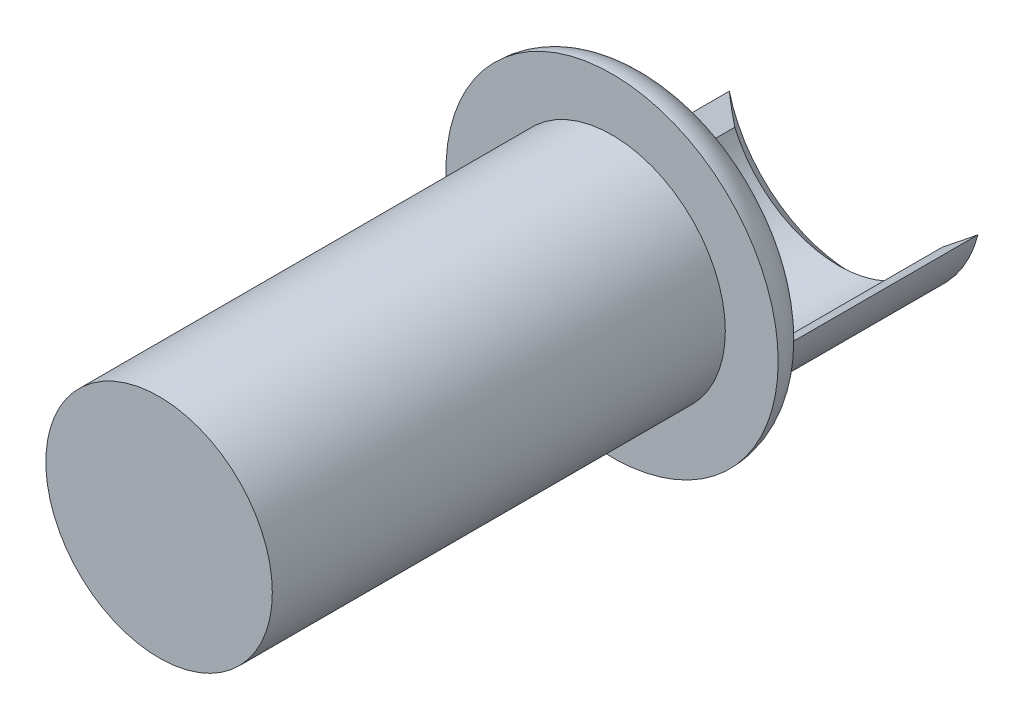
SolidWorks part; units mm, degrees
ref_plane "Plan de face" through (0, 0, 0) normal (0, 0, 1) x (1, 0, 0)
ref_plane "Plan de dessus" through (0, 0, 0) normal (0, 1, 0) x (1, 0, 0)
ref_plane "Plan de droite" through (0, 0, 0) normal (1, 0, 0) x (0, 0, -1)
sketch "Esquisse1" plane through (0, 0, 0) normal (0, 0, 1) x (1, 0, 0)
  circle A0 centre (0, 0) radius 22
extrude "Boss.-Extru.1" add sketch "Esquisse1" along normal blind 5
sketch "Esquisse2" plane through (0, 0, 5) normal (0, 0, 1) x (1, 0, 0)
  circle A0 centre (0, 0) radius 15
extrude "Enlèv. mat.-Extru.1" cut sketch "Esquisse2" against normal blind 5
sketch "Esquisse5" plane through (0, 0, 5) normal (0, 0, 1) x (1, 0, 0)
  circle A0 centre (0, 0) radius 15
extrude "Boss.-Extru.3" add sketch "Esquisse5" along normal blind 60 separate body
sketch "Esquisse6" plane through (0, 0, 5) normal (0, 0, -1) x (-1, 0, 0)
  line L0 (17, 0) -> (15, 0)
  line L1 (-15, 0) -> (-17, 0)
  arc A0 (-17, 0) -> (17, 0) centre (0, 0) ccw
  arc A1 (-15, 0) -> (15, 0) centre (0, 0) ccw
  circle A2 centre (0, 0) radius 15 construction
  circle A3 centre (0, 0) radius 15 construction
extrude "Boss.-Extru.4" add sketch "Esquisse6" along normal blind 40
fillet "Congé3" radius 5 1 edges at (22, 0, 0)
chamfer "Chanfrein1" distance 10 angle 45 1 edges at (-15, 0, -17.5)
chamfer "Chanfrein2" distance 10 angle 45 1 edges at (15, 0, -17.5)
chamfer "Chanfrein3" distance 10 angle 45 1 edges at (0, -15, -35)
sketch "Esquisse8" plane through (0, 0, 5) normal (0, 0, -1) x (-1, 0, 0)
  point P0 (0, 0)
